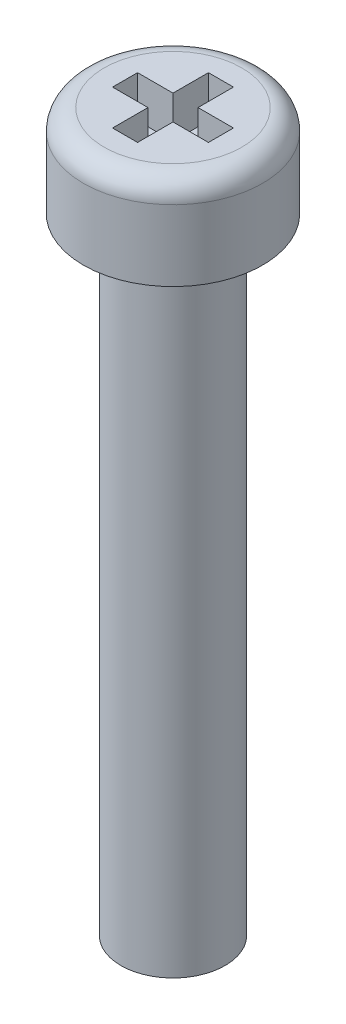
SolidWorks part; units mm, degrees
material "PVC Rigid"
ref_plane "Front Plane" through (0, 0, 0) normal (0, 0, 1) x (1, 0, 0)
ref_plane "Top Plane" through (0, 0, 0) normal (0, 1, 0) x (1, 0, 0)
ref_plane "Right Plane" through (0, 0, 0) normal (1, 0, 0) x (0, 0, -1)
other "Configuration Table"
ref_axis "AX-BOLT" through (0, 2.766, 0) along (0, -1, 0)
sketch "Sketch2" plane through (0, 0, 0) normal (0, 1, 0) x (1, 0, 0)
  circle A0 centre (0, 0) radius 1.25
  dimension "D1" = 2.5
extrude "Shaft" add sketch "Sketch2" against normal blind 15
sketch "Sketch3" plane through (0, 0, 0) normal (0, 0, 1) x (1, 0, 0)
  line L0 (0, 0) -> (0, 2.2) construction
  line L1 (0, 0) -> (0, 2.2)
  line L6 (0, 0) -> (2.15, 0)
  line L8 (0, 2.2) -> (1.65, 2.2)
  line L9 (2.15, 0) -> (2.15, 1.7)
  arc A0 (2.15, 1.7) -> (1.65, 2.2) centre (1.65, 1.7) ccw
  point P8 (2.15, 2.2)
  dimension "D3" = 0.5
  dimension "D1" = 4.3
  dimension "D2" = 2.2
revolve "Head" add sketch "Sketch3" angle 360 about L0
sketch "Sketch5" plane through (0, 2.2, 0) normal (0, 1, 0) x (1, 0, 0)
  line L0 (0, 2.15) -> (2.15, 2.15) construction
  line L1 (-0.3, -1.15) -> (0.3, -1.15)
  line L2 (-0.3, -1.15) -> (-0.3, -0.3)
  line L3 (-0.3, 1.15) -> (0.3, 1.15)
  line L4 (0.3, -1.15) -> (0.3, -0.3)
  line L5 (-0.3, -1.15) -> (0.3, 1.15) construction
  line L6 (-0.3, 1.15) -> (0.3, -1.15) construction
  line L7 (2.15, 0) -> (2.15, 2.15) construction
  line L8 (0, 0) -> (2.15, 2.15) construction
  line L9 (1.15, -0.3) -> (1.15, 0.3)
  line L10 (-1.15, 0.3) -> (-0.3, 0.3)
  line L11 (-1.15, -0.3) -> (-1.15, 0.3)
  line L12 (-1.15, -0.3) -> (-0.3, -0.3)
  line L13 (0.3, 0.3) -> (1.15, 0.3)
  line L14 (-0.3, 0.3) -> (-0.3, 1.15)
  line L15 (0.3, 0.3) -> (0.3, 1.15)
  line L16 (0.3, -0.3) -> (1.15, -0.3)
  circle A2 centre (0, 0) radius 2.15 construction
  point P0 (0, 0)
  dimension "D1" = 1
  dimension "D2" = 0.6
extrude "Philips" cut sketch "Sketch5" against normal blind 1
sketch "Sketch6" plane through (0, 0, 0) normal (0, 0, 1) x (1, 0, 0)
  line L5 (-0.3, 2.2) -> (0.3, 2.2) construction
  line L8 (0.3, 1.2) -> (0.3, 2.2) construction
  line L9 (-0.3, 1.2) -> (-0.3, 2.2) construction
  line L10 (-0.3, 2.2) -> (0.3, 2.2)
  line L12 (0.3, 1.44) -> (0.3, 2.2)
  line L13 (-0.3, 1.44) -> (-0.3, 2.2)
  line L14 (-0.3, 1.44) -> (0.3, 1.44)
  dimension "D1" = 0.76
extrude "Slot" [suppressed] cut sketch "Sketch6" against normal through all both and the other way through all
